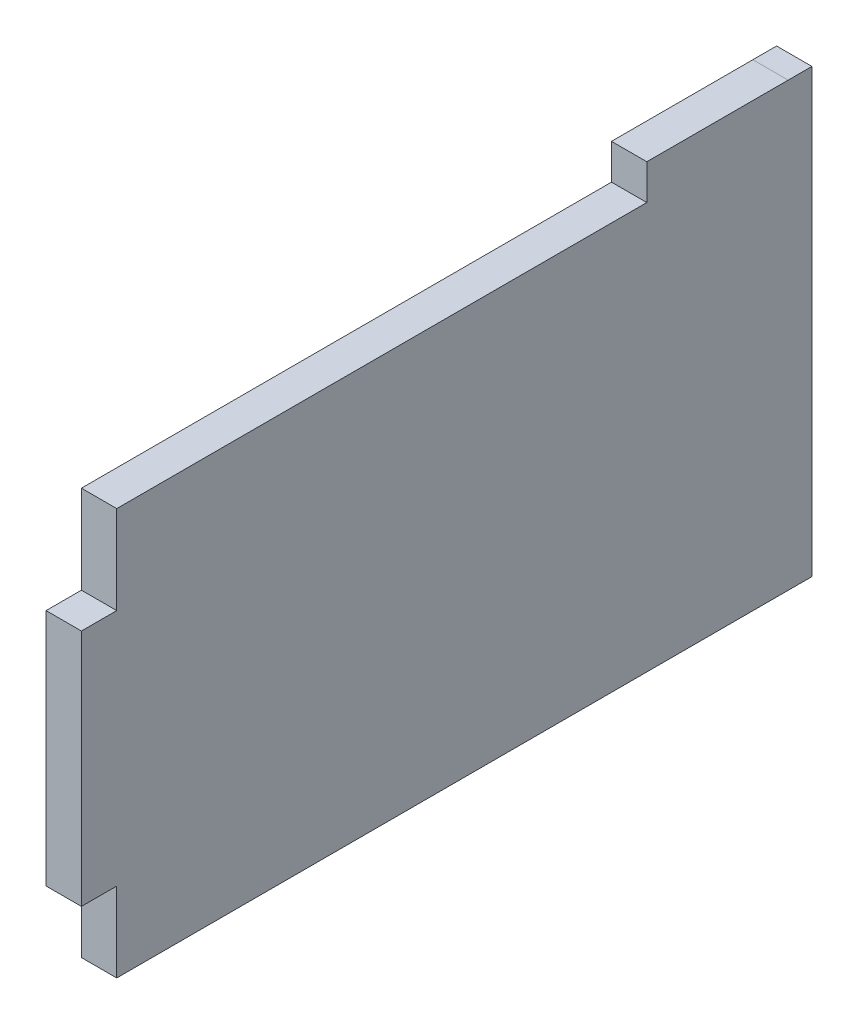
SolidWorks part; units mm, degrees
ref_plane "Front Plane" through (0, 0, 0) normal (0, 0, 1) x (1, 0, 0)
ref_plane "Top Plane" through (0, 0, 0) normal (0, 1, 0) x (1, 0, 0)
ref_plane "Right Plane" through (0, 0, 0) normal (1, 0, 0) x (0, 0, -1)
sketch "Sketch2" plane through (0, 0, 0) normal (1, 0, 0) x (0, 0, -1)
  line L1 (61, 4) -> (101, 4)
  line L3 (1, -46.0154) -> (161.7817, -46.0154)
  line L5 (-3, -10) -> (-3, -37)
  line L10 (1, 0) -> (61, 0)
  line L11 (61, 4) -> (61, 0)
  line L12 (101, 4) -> (101, 0)
  line L13 (165.7817, -10) -> (165.7817, -37)
  line L14 (101, 0) -> (161.7817, 0)
  line L16 (1, 0) -> (1, -10)
  line L17 (-3, -10) -> (1, -10)
  line L18 (-3, -37) -> (1, -37)
  line L19 (1, -37) -> (1, -46.0154)
  line L20 (161.7817, 0) -> (161.7817, -10)
  line L21 (165.7817, -10) -> (161.7817, -10)
  line L22 (165.7817, -37) -> (161.7817, -37)
  line L23 (161.7817, -37) -> (161.7817, -46.0154)
  dimension "D1" = 4
  dimension "D2" = 27
  dimension "D3" = 4
  dimension "D4" = 4
  dimension "D5" = 10
  dimension "D6" = 40
  dimension "D8" = 50.0154
  dimension "D9" = 168.7817
extrude "Boss-Extrude1" add sketch "Sketch2" along normal blind 4
sketch "Sketch3" plane through (0, 0, 0) normal (1, 0, 0) x (0, 0, -1)
  line L0 (77, 4.5941) -> (187.1394, 4.5941)
  line L4 (77, -46.9867) -> (77, 4.5941)
  line L5 (187.1394, 4.5941) -> (187.1394, -56.7775)
  line L6 (187.1394, -56.7775) -> (77, -56.7775)
  line L7 (77, -56.7775) -> (77, -46.9867)
extrude "Cut-Extrude1" cut sketch "Sketch3" along normal blind 10 and the other way blind 10
sketch "Sketch4" plane through (0, 0, -77) normal (0, 0, -1) x (-1, 0, 0)
  line L0 (-4, 4) -> (-4, -46.0154) construction
  line L1 (-4, 3.9995) -> (0, 3.9995)
  line L2 (-4, 3.9995) -> (-4, -46.0154)
  line L3 (-4, -46.0154) -> (0, -46.0154)
  line L4 (0, 3.9995) -> (0, -46.0154)
extrude "Boss-Extrude3" add sketch "Sketch4" along normal blind 2.69
